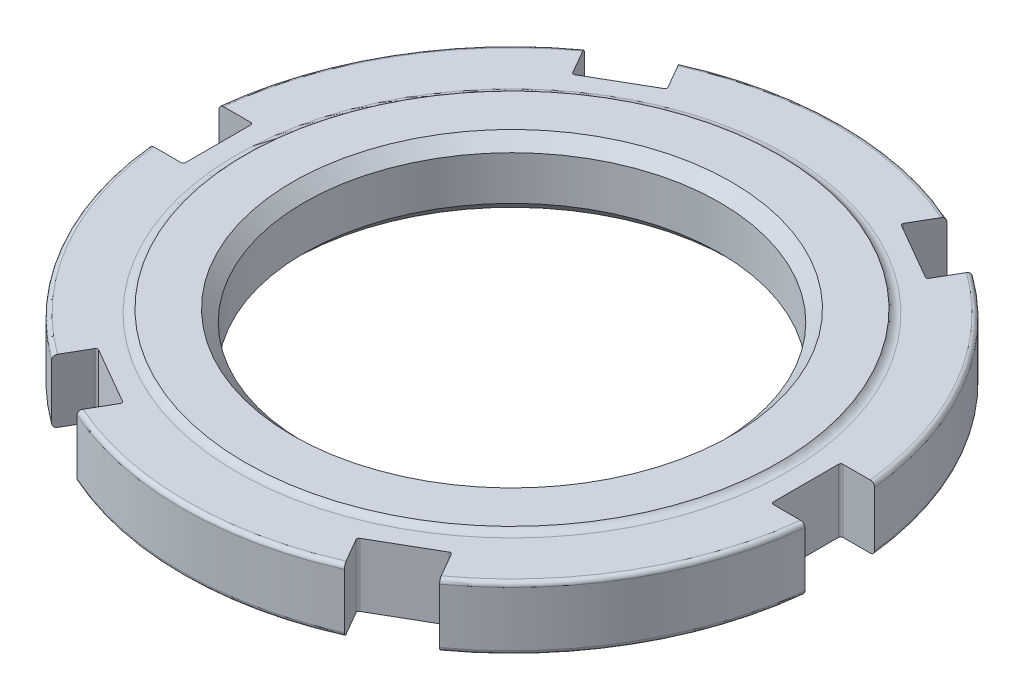
SolidWorks part; units mm, degrees
material "6061-T6 (SS)"
ref_plane "Front Plane" through (0, 0, 0) normal (0, 0, 1) x (1, 0, 0)
ref_plane "Top Plane" through (0, 0, 0) normal (0, 1, 0) x (1, 0, 0)
ref_plane "Right Plane" through (0, 0, 0) normal (1, 0, 0) x (0, 0, -1)
sketch "Sketch23" plane through (0, 0, 0) normal (0, 0, 1) x (1, 0, 0)
  line L0 (0, -46.91) -> (0, -156.1308) construction
  line L1 (24.6126, 0) -> (31.5849, 0)
  line L2 (31.5849, 0) -> (31.5849, -0.4826)
  line L3 (31.5849, -0.4826) -> (39.0398, -0.4826)
  line L4 (39.0398, -0.4826) -> (39.0398, -7.9883)
  line L5 (39.0398, -7.9883) -> (24.6126, -7.9883)
  line L8 (24.6126, -7.9883) -> (24.6126, 0)
  dimension "D1" = 63.1698
  dimension "D2" = 49.2252
  dimension "D3" = 78.0796
  dimension "D4" = 7.9883
  dimension "D6" = 7.5057
revolve "Revolve3" add sketch "Sketch23" angle 360 about L0
fillet "Fillet7" radius 1.27 1 edges at (0, -0.4826, 31.5849)
fillet "Fillet8" radius 0.508 2 edges at (0, -0.4826, 39.0398) (0, -7.9883, 39.0398)
chamfer "Chamfer2" distance 1.397 angle 45 2 edges at (0, 0, 24.6126) (0, -7.9883, 24.6126)
sketch "Sketch24" plane through (0, 0, 0) normal (0, 1, 0) x (1, 0, 0)
  line L0 (0, 0) -> (34.8107, 0) construction
  line L1 (51.1653, 4.1275) -> (34.8107, 4.1275)
  line L2 (51.1653, 4.1275) -> (51.1653, -4.1275)
  line L3 (51.1653, -4.1275) -> (34.8107, -4.1275)
  line L4 (34.8107, 4.1275) -> (34.8107, -4.1275)
  line L8 (0, 8.1387) -> (0, -7.2731) construction
  dimension "D1" = 8.255
  dimension "D2" = 69.6214
extrude "Cut-Extrude6" cut sketch "Sketch24" against normal up to surface (7.9883 mm away) up to face at (0, -7.9883, 26.0096)
fillet "Fillet6" radius 0.254 2 edges at (34.8107, -4.2355, 4.1275) (34.8107, -4.2355, -4.1275)
pattern_circular "CirPattern1" count 6 over 360 about axis through (0, -46.91, 0) along (0, 1, 0) of "Cut-Extrude6", "Fillet6"
